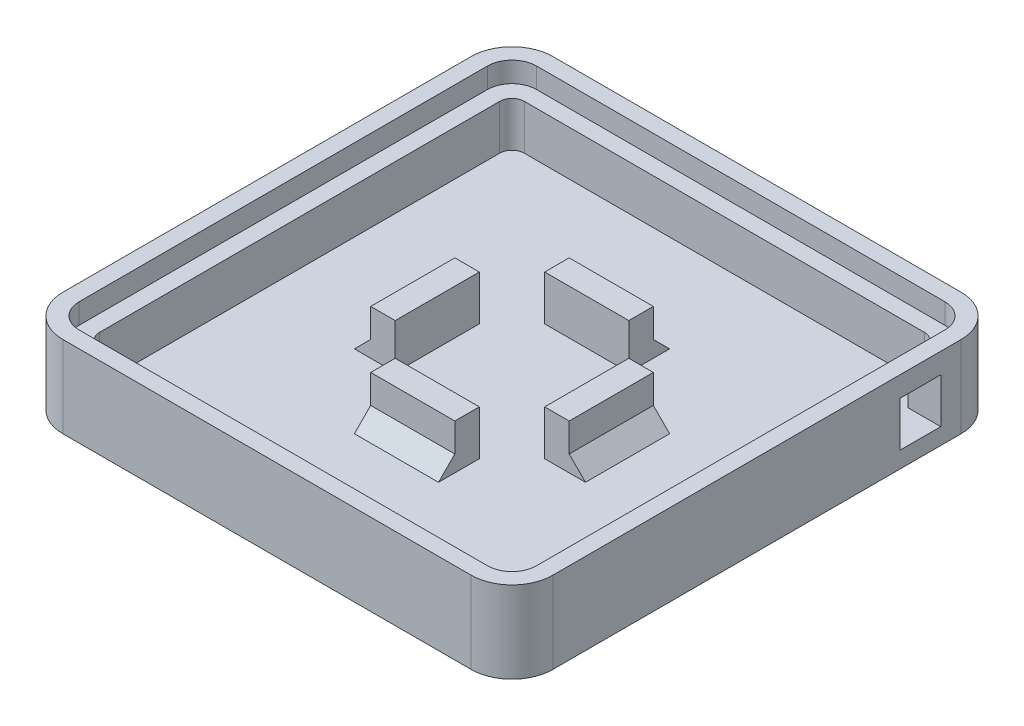
SolidWorks part; units mm, degrees
ref_plane "Plano frontal" through (0, 0, 0) normal (0, 0, 1) x (1, 0, 0)
ref_plane "Plano superior" through (0, 0, 0) normal (0, 1, 0) x (1, 0, 0)
ref_plane "Plano direito" through (0, 0, 0) normal (1, 0, 0) x (0, 0, -1)
sketch "Esboço1" plane through (0, 0, 0) normal (0, 1, 0) x (1, 0, 0)
  line L1 (-30, 30) -> (30, 30)
  line L2 (-30, 30) -> (-30, -30)
  line L3 (-30, -30) -> (30, -30)
  line L4 (30, 30) -> (30, -30)
  line L5 (-30, 30) -> (30, -30) construction
  line L6 (-30, -30) -> (30, 30) construction
  point P0 (0, 0)
  dimension "D1" = 60
  dimension "D2" = 60
extrude "Base" add sketch "Esboço1" along normal blind 2
sketch "Esboço3" plane through (0, 2, 0) normal (0, 1, 0) x (1, 0, 0)
  line L0 (-12.15, 12.15) -> (12.15, 12.15)
  line L1 (-9.15, 9.15) -> (9.15, 9.15)
  line L2 (-9.15, 9.15) -> (-9.15, -9.15)
  line L3 (-9.15, -9.15) -> (9.15, -9.15)
  line L4 (9.15, 9.15) -> (9.15, -9.15)
  line L5 (-9.15, 9.15) -> (9.15, -9.15) construction
  line L6 (-9.15, -9.15) -> (9.15, 9.15) construction
  line L7 (12.15, 12.15) -> (12.15, -12.15)
  line L8 (-12.15, -12.15) -> (12.15, -12.15)
  line L9 (-12.15, 12.15) -> (-12.15, -12.15)
  point P0 (0, 0)
  dimension "D1" = 18.3
  dimension "D2" = 18.3
  dimension "D3" = 3
extrude "Encaixes da Arvore" add sketch "Esboço3" along normal blind 5.5
sketch "Esboço4" plane through (0, 2, 0) normal (0, 1, 0) x (1, 0, 0)
  line L0 (-26, 26) -> (-26, -26)
  line L1 (-30, 30) -> (30, 30)
  line L2 (-30, 30) -> (-30, -30)
  line L3 (-30, -30) -> (30, -30)
  line L4 (30, 30) -> (30, -30)
  line L5 (-30, 30) -> (30, -30) construction
  line L6 (-30, -30) -> (30, 30) construction
  line L7 (-26, -26) -> (26, -26)
  line L8 (26, 26) -> (26, -26)
  line L9 (-26, 26) -> (26, 26)
  point P0 (0, 0)
  dimension "D1" = 4
extrude "Paredes" add sketch "Esboço4" along normal blind 8
sketch "Esboço5" plane through (0, 7.5, 0) normal (0, 1, 0) x (1, 0, 0)
  line L0 (0, 15.7353) -> (0, -14.3539) construction
  line L1 (-14.0363, 0) -> (14.8621, 0) construction
  line L2 (12.15, 5.15) -> (5.15, 5.15)
  line L3 (-12.15, 12.15) -> (-5.15, 12.15)
  line L4 (-12.15, 12.15) -> (-12.15, 5.15)
  line L5 (-12.15, 5.15) -> (-5.15, 5.15)
  line L6 (-5.15, 12.15) -> (-5.15, 5.15)
  line L7 (12.15, 12.15) -> (12.15, 5.15)
  line L8 (12.15, 12.15) -> (5.15, 12.15)
  line L9 (5.15, 12.15) -> (5.15, 5.15)
  line L10 (5.15, -12.15) -> (5.15, -5.15)
  line L11 (12.15, -12.15) -> (5.15, -12.15)
  line L12 (12.15, -12.15) -> (12.15, -5.15)
  line L13 (12.15, -5.15) -> (5.15, -5.15)
  line L14 (-12.15, -5.15) -> (-5.15, -5.15)
  line L15 (-12.15, -12.15) -> (-12.15, -5.15)
  line L16 (-12.15, -12.15) -> (-5.15, -12.15)
  line L17 (-5.15, -12.15) -> (-5.15, -5.15)
  point P25 (0, 0)
  dimension "D1" = 7
  dimension "D2" = 7
  dimension "D3" = 4
extrude "Corte dos Encaixe" cut sketch "Esboço5" against normal up to surface (5.5 mm away) up to face at (0, 2, 0)
fillet "Filete1" radius 5 1 edges at (-30, 5, 30) type face fillet first side face at (0, 5, 30) second side face at (-30, 5, 0)
fillet "Filete2" radius 5 1 edges at (-30, 5, -30) type face fillet first side face at (0, 5, -30) second side face at (-30, 5, -2.5)
fillet "Filete3" radius 5 1 edges at (30, 5, -30) type face fillet first side face at (30, 5, 0) second side face at (2.5, 5, -30)
fillet "Filete4" radius 5 1 edges at (30, 5, 30) type face fillet first side face at (2.5, 5, 30) second side face at (30, 5, 2.5)
sketch "Esboço6" plane through (0, 10, 0) normal (0, 1, 0) x (1, 0, 0)
  line L0 (-28, 28) -> (28, 28)
  line L1 (-26, -26) -> (26, -26)
  line L2 (-26, -26) -> (-26, 26)
  line L3 (-26, 26) -> (26, 26)
  line L4 (26, -26) -> (26, 26)
  line L5 (-26, -26) -> (26, 26) construction
  line L6 (-26, 26) -> (26, -26) construction
  line L7 (28, -28) -> (28, 28)
  line L8 (-28, -28) -> (28, -28)
  line L9 (-28, -28) -> (-28, 28)
  point P0 (0, 0)
  dimension "D1" = 52
  dimension "D2" = 52
  dimension "D3" = 2
extrude "Corte-extrusão2" cut sketch "Esboço6" against normal blind 2.5
fillet "Filete5" radius 1.5 4 edges at (26, 4.75, 26) (-26, 4.75, 26) (26, 4.75, -26) (-26, 4.75, -26)
fillet "Filete6" radius 3 4 edges at (-28, 8.75, -28) (-28, 8.75, 28) (28, 8.75, 28) (28, 8.75, -28)
sketch "Esboço7" plane through (26, 0, 0) normal (-1, 0, 0) x (0, 0, 1)
  line L0 (24.5, 2) -> (-24.5, 2) construction
  line L1 (-22.5, 2) -> (-17.5, 2)
  line L2 (-22.5, 2) -> (-22.5, 7.5)
  line L3 (-22.5, 7.5) -> (-17.5, 7.5)
  line L4 (-17.5, 2) -> (-17.5, 7.5)
  line L5 (-24.5, 7.5) -> (-24.5, 2) construction
  dimension "D1" = 5
  dimension "D2" = 5.5
  dimension "D3" = 2
extrude "Corte-extrusão3" cut sketch "Esboço7" against normal through all
chamfer "Chanfro2" distance 2 angle 45 4 edges at (-12.15, 2, 0) (0, 2, 12.15) (12.15, 2, 0) (0, 2, -12.15)
